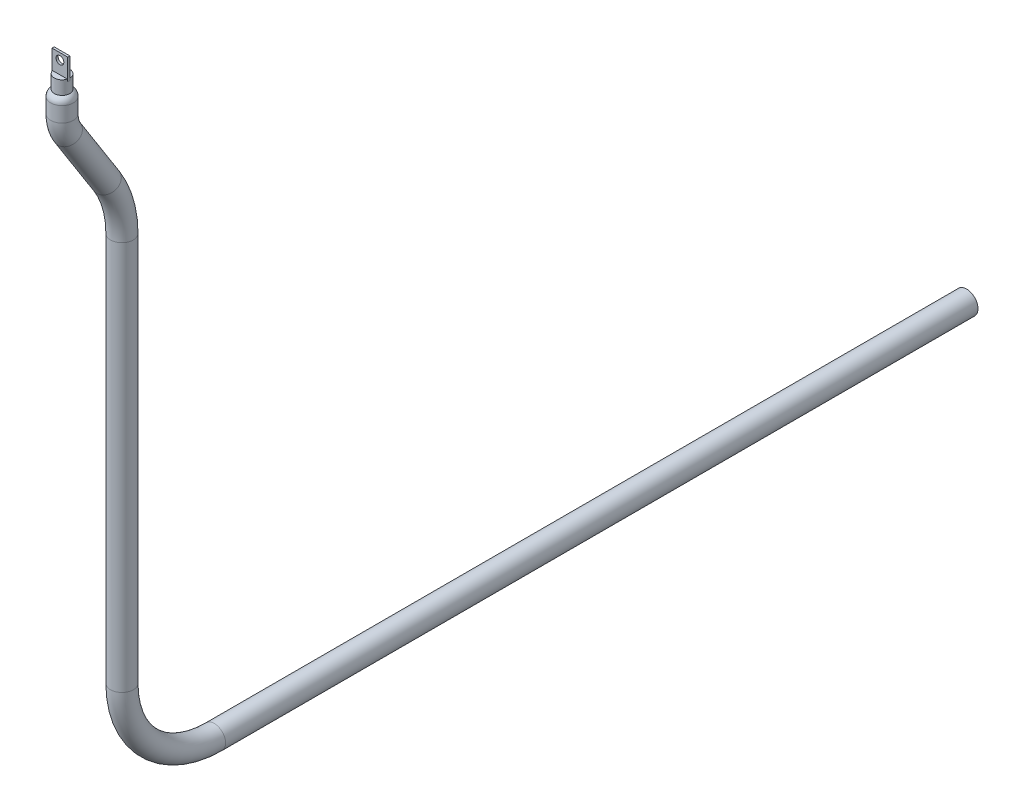
SolidWorks part; units mm, degrees
ref_plane "Alzado" through (0, 0, 0) normal (0, 0, 1) x (1, 0, 0)
ref_plane "Planta" through (0, 0, 0) normal (0, 1, 0) x (1, 0, 0)
ref_plane "Vista lateral" through (0, 0, 0) normal (1, 0, 0) x (0, 0, -1)
sketch3d "Croquis3D1"
  line L0 (-975.306, -247.4185, 3234.31) -> (-975.306, -277.4827, 3234.31)
  line L1 (-975.306, -304.2777, 3226.5241) -> (-975.306, -390.4905, 3171.8013)
  line L2 (-975.306, -465.5164, 3150.0007) -> (-975.306, -1014.0355, 3150.0007)
  line L3 (-975.306, -1144.0355, 3020.0007) -> (-975.306, -1144.0355, 1960.4972)
  arc A1 (-975.306, -390.4905, 3171.8013) -> (-975.306, -465.5164, 3150.0007) centre (-975.306, -465.5164, 3290.0007) ccw
  arc A2 (-975.306, -277.4827, 3234.31) -> (-975.306, -304.2777, 3226.5241) centre (-975.306, -277.4827, 3184.31) ccw
  arc A3 (-975.306, -1144.0355, 3020.0007) -> (-975.306, -1014.0355, 3150.0007) centre (-975.306, -1014.0355, 3020.0007) ccw
  point P12 (-975.306, -424.8361, 3150.0007)
  point P13 (-1115.306, -465.5164, 3290.0007)
  point P16 (-975.306, -292.0114, 3234.31)
  point P17 (-925.306, -277.4827, 3184.31)
  point P20 (-975.306, -1144.0355, 3150.0007)
  point P21 (-1105.306, -1014.0355, 3020.0007)
  dimension "D3" = 130
sweep "Barrer1" add path "Croquis3D1" circular profile diameter 32 parameters "D3"=32
sketch "Croquis13" plane through (0, -247.4185, 0) normal (0, 1, 0) x (1, 0, 0)
  line L0 (-975.0352, -3233.754) -> (-975.306, -3250.31) construction
  line L1 (-975.306, -3250.31) -> (-975.306, -3234.31) construction
  line L2 (-975.306, -3234.31) -> (-837.0067, -3234.31) construction
  circle A0 centre (-975.306, -3234.31) radius 16 construction
ref_plane "Plano1" through (0, 0, 3234.31) normal (0, 0, 1) x (1, 0, 0)
sketch "Croquis14" plane through (0, 0, 3234.31) normal (0, 0, 1) x (1, 0, 0)
  line L0 (-975.306, -247.4185) -> (-975.306, -210.5251) construction
  line L1 (-975.306, -247.4185) -> (-837.0067, -247.4185) construction
  line L2 (-959.306, -247.4185) -> (-991.306, -247.4185) construction
  line L3 (-986.306, -231.3305) -> (-964.306, -231.3305)
  line L4 (-986.306, -231.3305) -> (-986.306, -201.3305)
  line L5 (-986.306, -201.3305) -> (-964.306, -201.3305)
  line L6 (-964.306, -231.3305) -> (-964.306, -201.3305)
  line L7 (-986.306, -231.3305) -> (-964.306, -201.3305) construction
  line L8 (-986.306, -201.3305) -> (-964.306, -231.3305) construction
  circle A0 centre (-975.306, -210.5251) radius 5.5
  point P5 (-975.306, -216.3305)
  dimension "D1" = 11
  dimension "D2" = 22
  dimension "D3" = 30
extrude "Saliente-Extruir1" add sketch "Croquis14" along normal blind 3 separate body
sketch "Croquis15" plane through (0, -247.4185, 0) normal (0, 1, 0) x (1, 0, 0)
  circle A0 centre (-975.306, -3234.31) radius 10.8411
extrude "Saliente-Extruir2" add sketch "Croquis15" along normal blind 19
fillet "Redondeo1" radius 10 1 edges at (-959.306, -247.4185, 3234.31)
